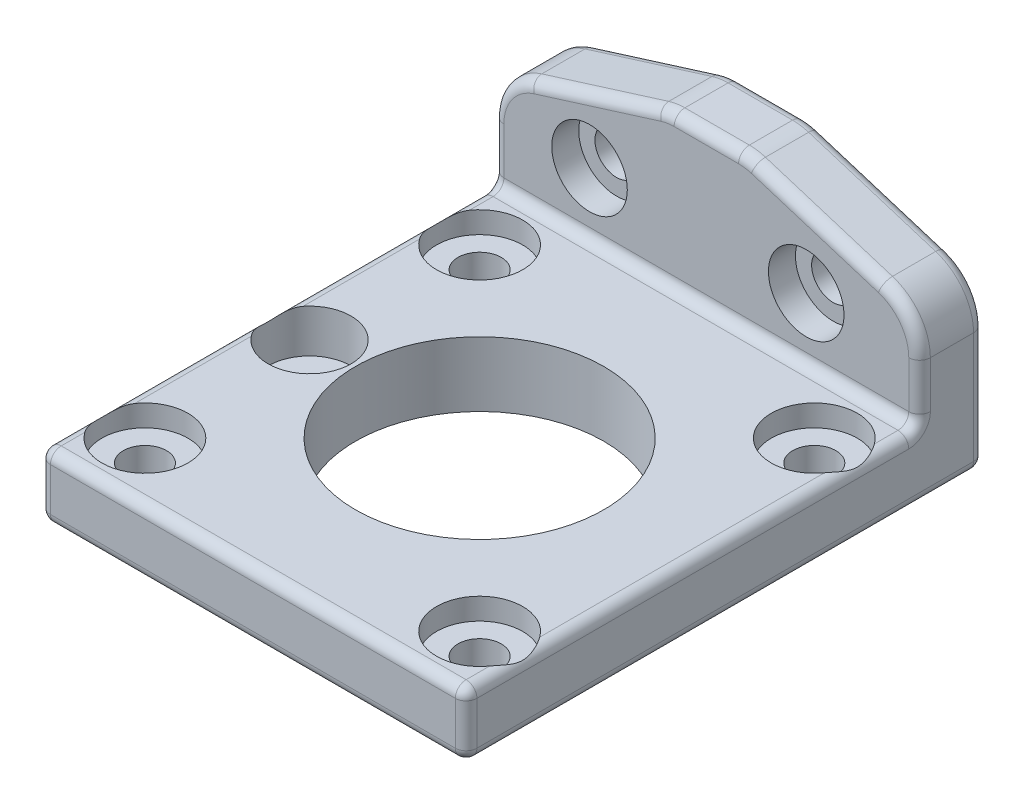
SolidWorks part; units mm, degrees
ref_plane "Front Plane" through (0, 0, 0) normal (0, 0, 1) x (1, 0, 0)
ref_plane "Top Plane" through (0, 0, 0) normal (0, 1, 0) x (1, 0, 0)
ref_plane "Right Plane" through (0, 0, 0) normal (1, 0, 0) x (0, 0, -1)
sketch "Sketch1" plane through (0, 0, 0) normal (0, 1, 0) x (1, 0, 0)
  line L1 (-19.75, 21) -> (19.75, 21)
  line L2 (-19.75, 21) -> (-19.75, -21)
  line L3 (-19.75, -21) -> (19.75, -21)
  line L4 (19.75, 21) -> (19.75, -21)
  line L5 (-19.75, 21) -> (19.75, -21) construction
  line L6 (-19.75, -21) -> (19.75, 21) construction
  point P0 (0, 0)
  dimension "D1" = 39.5
  dimension "D2" = 42
extrude "Boss-Extrude1" add sketch "Sketch1" along normal blind 6
sketch "Sketch3" plane through (0, 6, 0) normal (0, 1, 0) x (1, 0, 0)
  line L0 (0, -15.5) -> (0, 15.5) construction
  line L1 (-15.5, 0) -> (15.5, 0) construction
  line L2 (-15.5, 15.5) -> (15.5, 15.5) construction
  line L3 (15.5, 15.5) -> (15.5, -15.5) construction
  line L4 (15.5, -15.5) -> (-15.5, -15.5) construction
  line L5 (-15.5, -15.5) -> (-15.5, 15.5) construction
  circle A0 centre (-15.5, 15.5) radius 3.9905
  circle A1 centre (15.5, 15.5) radius 3.9905
  circle A2 centre (-15.5, -15.5) radius 3.9905
  circle A3 centre (15.5, -15.5) radius 3.9905
  point P12 (0, 0)
  point P16 (0, 0)
  point P17 (0, 15.5)
  point P20 (15.5, 0)
  dimension "D1" = 7.981
  dimension "D2" = 31
  dimension "D3" = 31
extrude "Cut-Extrude1" cut sketch "Sketch3" against normal blind 2
sketch "Sketch4" plane through (0, 6, 0) normal (0, 1, 0) x (1, 0, 0)
  circle A0 centre (0, 0) radius 11.5
  circle A1 centre (15.5, 15.5) radius 2
  circle A2 centre (-15.5, 15.5) radius 2
  circle A3 centre (-15.5, -15.5) radius 2
  circle A4 centre (15.5, -15.5) radius 2
  dimension "D1" = 4
  dimension "D2" = 23
extrude "Cut-Extrude2" cut sketch "Sketch4" against normal through all
sketch "Sketch5" plane through (0, 0, -21) normal (0, 0, -1) x (-1, 0, 0)
  line L0 (0, 7.5) -> (0, 12.125) construction
  line L2 (-19.75, 15) -> (-19.75, 0)
  line L3 (-19.75, 0) -> (19.75, 0)
  line L4 (19.75, 15) -> (19.75, 0)
  line L5 (-19.75, 15) -> (19.75, 0) construction
  line L6 (-19.75, 0) -> (19.75, 15) construction
  line L7 (-3.75, 20) -> (3.75, 20)
  line L11 (19.75, 15) -> (-27.0447, 15) construction
  line L13 (3.75, 20) -> (19.75, 15)
  line L14 (-3.75, 20) -> (-19.75, 15)
  point P0 (0, 7.5)
  point P6 (0, 27.5)
  point P7 (-19.75, 15)
  dimension "D1" = 20
  dimension "D2" = 15
  dimension "D3" = 16
  dimension "D4" = 16
extrude "Boss-Extrude2" add sketch "Sketch5" along normal blind 6
sketch "Sketch6" plane through (0, 0, -21) normal (0, 0, 1) x (1, 0, 0)
  line L0 (-10.82, 11.75) -> (9.25, 11.75) construction
  line L1 (19.75, 6.7748) -> (-0.785, 6.7748) construction
  line L2 (19.75, 15) -> (19.75, 6) construction
  line L3 (-0.785, 6.7748) -> (-0.785, 11.75) construction
  circle A0 centre (-10.82, 11.75) radius 3.5
  circle A1 centre (9.25, 11.75) radius 3.5
  dimension "D1" = 7
  dimension "D2" = 7
  dimension "D3" = 20.535
  dimension "D4" = 20.07
  dimension "D5" = 11.75
extrude "Cut-Extrude3" cut sketch "Sketch6" against normal blind 2.5
sketch "Sketch7" plane through (0, 0, -21) normal (0, 0, 1) x (1, 0, 0)
  circle A0 centre (-10.82, 11.75) radius 2
  circle A1 centre (9.25, 11.75) radius 2
  dimension "D1" = 4
extrude "Cut-Extrude4" cut sketch "Sketch7" against normal through all
fillet "Fillet1" radius 5 4 edges at (19.75, 15, -24) (3.75, 20, -24) (-3.75, 20, -24) (-19.75, 15, -24)
sketch "Sketch8" plane through (0, 6, 0) normal (0, 1, 0) x (1, 0, 0)
  line L0 (0, 0) -> (-15.75, 0) construction
  circle A0 centre (-15.75, 0) radius 3.8413
  dimension "D1" = 7.6825
  dimension "D2" = 15.75
extrude "Cut-Extrude5" cut sketch "Sketch8" against normal blind 4
fillet "Fillet2" radius 1 28 edges at (0, 20, -21) (3.7413, 19.9428, -21) (-3.7413, 19.9428, -21) (10.3598, 17.9344, -21) (-10.3598, 17.9344, -21) (18.7785, 14.2857, -21) (-18.7785, 14.2857, -21) (19.75, 8.662, -21) (-19.75, 8.662, -21) (-19.75, 5.662, -27) (-18.7785, 14.2857, -27) (-10.3598, 17.9344, -27) (-3.7413, 19.9428, -27) (19.75, 5.662, -27) (18.7785, 14.2857, -27) (10.3598, 17.9344, -27) (3.7413, 19.9428, -27) (0, 0, -27) (0, 20, -27) (0, 6, -21) (0, 0, 21) (0, 6, 21) (19.75, 0, -3) (19.75, 6, 0) (-19.75, 0, -3) (-19.75, 6, 0) (-19.75, 3, 21) (19.75, 3, 21)
